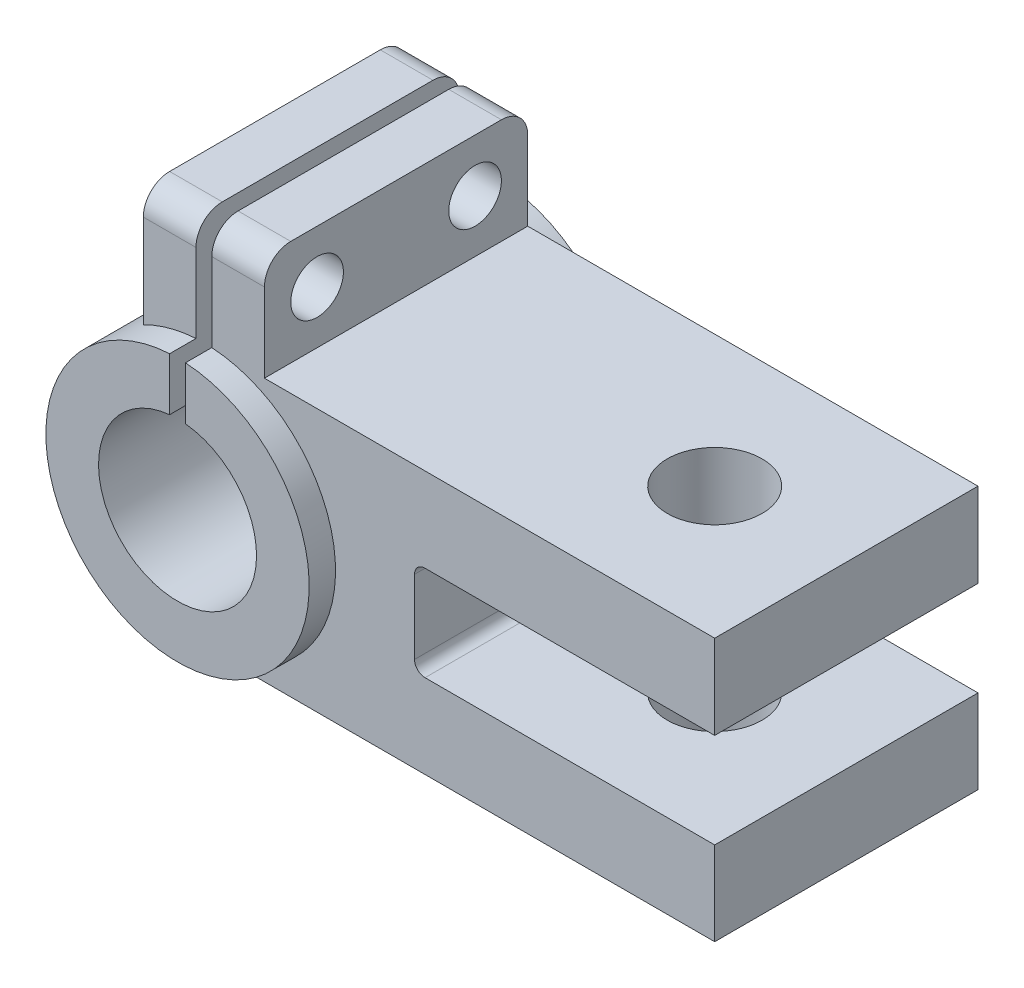
SolidWorks part; units mm, degrees
ref_plane "Piano frontale" through (0, 0, 0) normal (0, 0, 1) x (1, 0, 0)
ref_plane "Piano superiore" through (0, 0, 0) normal (0, 1, 0) x (1, 0, 0)
ref_plane "Piano destro" through (0, 0, 0) normal (1, 0, 0) x (0, 0, -1)
sketch "Schizzo1" plane through (0, 0, 0) normal (0, 0, 1) x (1, 0, 0)
  line L0 (-11.5, 22.198) -> (-11.5, 44.9248)
  line L1 (-11.5, 44.9248) -> (-1.5, 44.9248)
  line L2 (-1.5, 44.9248) -> (-1.5, 14.9248)
  line L3 (0, 0) -> (0, 48.8657) construction
  line L4 (1.5, 44.9248) -> (1.5, 14.9248)
  line L5 (11.5, 44.9248) -> (1.5, 44.9248)
  line L6 (11.5, 22.198) -> (11.5, 44.9248)
  line L7 (11.5, 24.9248) -> (97, 24.9248)
  line L8 (97, 24.9248) -> (97, 8.9248)
  line L9 (97, 8.9248) -> (40, 8.9248)
  line L10 (40, 8.9248) -> (40, -9.0752)
  line L11 (40, -9.0752) -> (97, -9.0752)
  line L12 (97, -9.0752) -> (97, -25)
  line L13 (97, -25) -> (0, -25)
  circle A0 centre (0, 0) radius 25
  circle A1 centre (0, 0) radius 15
  point P20 (0, 0)
  point P22 (-11.5, 45.152)
  point P23 (89.0531, 24.3355)
  dimension "D1" = 50
  dimension "D2" = 30
  dimension "D3" = 3
  dimension "D4" = 23
  dimension "D5" = 20
  dimension "D6" = 18
  dimension "D7" = 57
  dimension "D8" = 57
  dimension "D9" = 30
  dimension "D10" = 40
  dimension "D11" = 16
extrude "Estrusione-Estrusione3" add sketch "Schizzo1" along normal mid plane 60 contours A1 L2 A0 L4 region at (-6.4567, 23.4195, 0)
extrude "Estrusione-Estrusione4" add sketch "Schizzo1<3>" along normal mid plane 50 contours A0 L13 L12 L11 L10 L9 L8 L7 L6 | A0 L6 L5 L4 | A0 L2 L1 L0 region at (-6.6085, 34.4236, 0) region at (18.4491, -18.4491, 0) region at (6.6085, 34.4236, 0)
sketch "Schizzo1<3>" plane through (0, 0, 0) normal (0, 0, 1) x (1, 0, 0) same geometry as "Schizzo1"
hole_wizard "Foro Ø18.0 (18)-1" positions "Schizzo2" profile "Schizzo3" hole size "Ø18.0" standard "ISO" end condition through all
sketch "Schizzo2" plane through (0, -25, 0) normal (0, -1, 0) x (-1, 0, 0)
  line L0 (0, 0) -> (-116.4595, 0) construction
  line L2 (-72, 25) -> (-72, -25) construction
  line L3 (-97, 25) -> (0, 25) construction
  line L4 (-97, -25) -> (0, -25) construction
  line L6 (25, 30) -> (-25, 30) construction
  point P16 (-72, 0)
  dimension "D1" = 30
  dimension "D2" = 72
sketch "Schizzo3" plane through (72, -25, 0) normal (1, 0, 0) x (0, 0, -1)
  line L0 (0, 0) -> (0, 69.9248)
  line L1 (0, 69.9248) -> (9, 69.9248)
  line L2 (9, 69.9248) -> (9, 0)
  line L5 (9, 0) -> (0, 0)
  line L11 (0, -6.35) -> (0, 107.95) construction
  dimension "Thru Hole Dia." = 18
  dimension "Thru Hole Depth" = 69.9248
hole_wizard "Foro Ø10.0 (10)-1" positions "Schizzo4" profile "Schizzo5" hole size "Ø10.0" standard "ISO" end condition through all
sketch "Schizzo4" plane through (-11.5, 0, 0) normal (-1, 0, 0) x (0, 0, 1)
  line L0 (-15, 44.9248) -> (-15, 22.198) construction
  line L1 (25, 44.9248) -> (-25, 44.9248) construction
  line L2 (25, 22.198) -> (-25, 22.198) construction
  line L11 (0, 0) -> (0, 56.3717) construction
  line L13 (-25, 34.9248) -> (0, 34.9248) construction
  line L14 (-25, 22.198) -> (-25, 44.9248) construction
  point P33 (-15, 34.9248)
  point P36 (0, 0)
  point P37 (15, 34.9248)
  dimension "D1" = 15
  dimension "D2" = 10
sketch "Schizzo5" plane through (-11.5, 34.9248, 15) normal (0, 1, 0) x (0, 0, 1)
  line L0 (0, 0) -> (0, 108.5)
  line L1 (0, 108.5) -> (5, 108.5)
  line L2 (5, 108.5) -> (5, 0)
  line L5 (5, 0) -> (0, 0)
  line L11 (0, -6.35) -> (0, 107.95) construction
  dimension "Thru Hole Dia." = 10
  dimension "Thru Hole Depth" = 108.5
fillet "Raccordo1" radius 5 4 edges at (-6.5, 44.9248, 25) (6.5, 44.9248, 25) (-6.5, 44.9248, -25) (6.5, 44.9248, -25)
fillet "Raccordo2" radius 2 2 edges at (40, -9.0752, 0) (40, 8.9248, 0)
